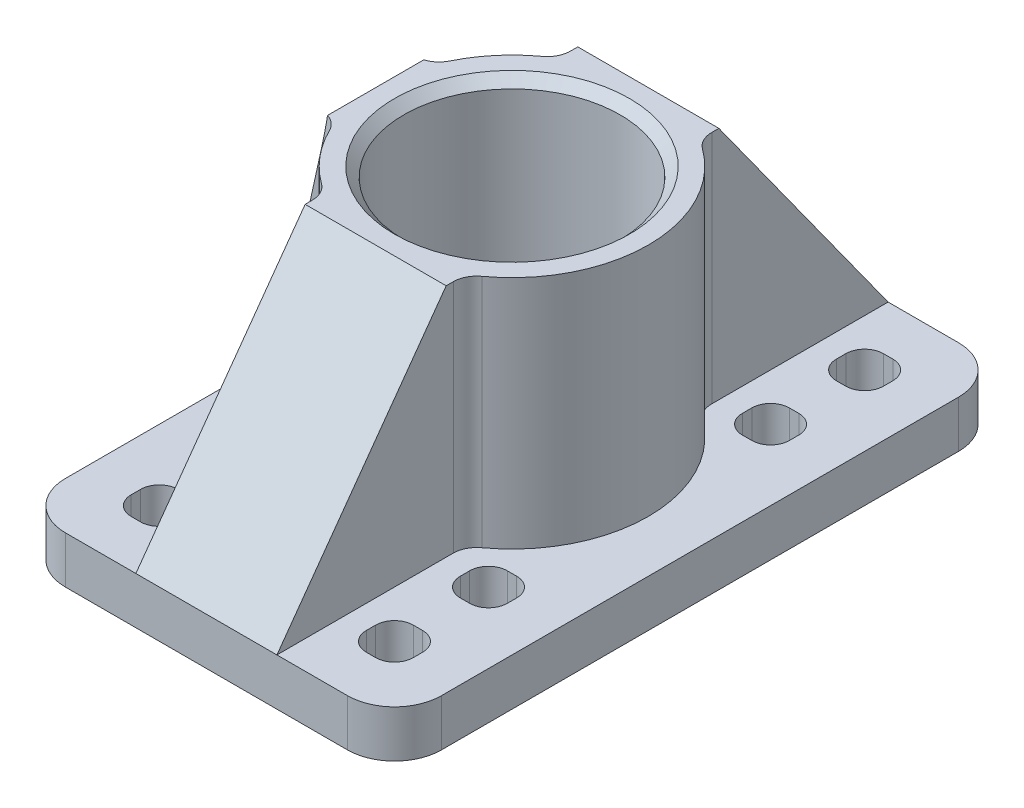
SolidWorks part; units mm, degrees
ref_plane "Front Plane" through (0, 0, 0) normal (0, 0, 1) x (1, 0, 0)
ref_plane "Top Plane" through (0, 0, 0) normal (0, 1, 0) x (1, 0, 0)
ref_plane "Right Plane" through (0, 0, 0) normal (1, 0, 0) x (0, 0, -1)
sketch "Sketch1" plane through (0, 0, 0) normal (0, 1, 0) x (1, 0, 0)
  line L0 (0, 0) -> (9794.4102, 0) construction
  line L1 (0, 0) -> (0, -9794.4102) construction
  line L2 (-12.5, 15) -> (12.5, 15) construction
  line L3 (-15, 17.5) -> (-10, 17.5)
  line L4 (-15, 17.5) -> (-15, 12.5)
  line L5 (-15, 12.5) -> (-10, 12.5)
  line L6 (-10, 17.5) -> (-10, 12.5)
  line L7 (-15, 17.5) -> (-10, 12.5) construction
  line L8 (-15, 12.5) -> (-10, 17.5) construction
  line L9 (12.5, -15) -> (12.5, 15) construction
  line L10 (-12.5, -15) -> (-12.5, 15) construction
  line L11 (-12.5, -15) -> (12.5, -15) construction
  line L12 (-12.5, -15) -> (-12.5, -25) construction
  line L13 (-15, -12.5) -> (-10, -12.5)
  line L14 (-15, -12.5) -> (-15, -17.5)
  line L15 (-15, -17.5) -> (-10, -17.5)
  line L16 (-10, -12.5) -> (-10, -17.5)
  line L17 (-15, -12.5) -> (-10, -17.5) construction
  line L18 (-15, -17.5) -> (-10, -12.5) construction
  line L19 (10, 17.5) -> (15, 17.5)
  line L20 (10, 17.5) -> (10, 12.5)
  line L21 (10, 12.5) -> (15, 12.5)
  line L22 (15, 17.5) -> (15, 12.5)
  line L23 (10, 17.5) -> (15, 12.5) construction
  line L24 (10, 12.5) -> (15, 17.5) construction
  line L25 (10, -12.5) -> (15, -12.5)
  line L26 (10, -12.5) -> (10, -17.5)
  line L27 (10, -17.5) -> (15, -17.5)
  line L28 (15, -12.5) -> (15, -17.5)
  line L29 (10, -12.5) -> (15, -17.5) construction
  line L30 (10, -17.5) -> (15, -12.5) construction
  line L31 (-12.5, -25) -> (12.5, -25) construction
  line L32 (12.5, -25) -> (12.5, -15) construction
  line L33 (-15, 22.5) -> (-10, 27.5) construction
  line L34 (-15, -27.5) -> (-10, -27.5)
  line L35 (-15, -27.5) -> (-15, -22.5)
  line L36 (-15, -22.5) -> (-10, -22.5)
  line L37 (-10, -27.5) -> (-10, -22.5)
  line L38 (-15, -27.5) -> (-10, -22.5) construction
  line L39 (-15, -22.5) -> (-10, -27.5) construction
  line L40 (10, -27.5) -> (15, -27.5)
  line L41 (10, -27.5) -> (10, -22.5)
  line L42 (10, -22.5) -> (15, -22.5)
  line L43 (15, -27.5) -> (15, -22.5)
  line L44 (10, -27.5) -> (15, -22.5) construction
  line L45 (10, -22.5) -> (15, -27.5) construction
  line L46 (-15, 27.5) -> (-10, 22.5) construction
  line L47 (-12.5, 15) -> (-12.5, 25) construction
  line L48 (-10, 27.5) -> (-10, 22.5)
  line L49 (-15, 22.5) -> (-10, 22.5)
  line L50 (-15, 27.5) -> (-15, 22.5)
  line L51 (-15, 27.5) -> (-10, 27.5)
  line L52 (10, 22.5) -> (15, 27.5) construction
  line L53 (10, 27.5) -> (15, 22.5) construction
  line L54 (12.5, 25) -> (12.5, 15) construction
  line L55 (-12.5, 25) -> (12.5, 25) construction
  line L56 (15, 27.5) -> (15, 22.5)
  line L57 (10, 22.5) -> (15, 22.5)
  line L58 (10, 27.5) -> (10, 22.5)
  line L59 (10, 27.5) -> (15, 27.5)
  line L61 (-20, 32.5) -> (20, 32.5)
  line L62 (-20, 32.5) -> (-20, -32.5)
  line L63 (-20, -32.5) -> (20, -32.5)
  line L64 (20, 32.5) -> (20, -32.5)
  line L65 (-20, 32.5) -> (20, -32.5) construction
  line L66 (-20, -32.5) -> (20, 32.5) construction
  point P5 (-12.5, 15)
  point P15 (0, 15)
  point P16 (-12.5, 0)
  point P17 (12.5, 0)
  point P50 (0, 0)
  dimension "D1" = 5
  dimension "D2" = 30
  dimension "D3" = 25
  dimension "D4" = 5
  dimension "D5" = 5
  dimension "D6" = 5
extrude "MountBase" add sketch "Sketch1" along normal blind 5
sketch "Sketch4" plane through (0, 5, 0) normal (0, 1, 0) x (1, 0, 0)
  line L0 (0, 0) -> (50000, 0) construction
  line L1 (0, 0) -> (0, -50000) construction
  line L2 (-14.5, 5) -> (-14.5, -5)
  line L3 (-14.5, -5) -> (-13.6107, -5)
  line L5 (-13.6107, 5) -> (-14.5, 5)
  line L6 (14.5, -5) -> (13.6107, -5)
  line L7 (14.5, 5) -> (14.5, -5)
  line L8 (13.6107, 5) -> (14.5, 5)
  line L9 (-7.5, 14.5) -> (7.5, 14.5)
  line L10 (7.5, 14.5) -> (7.5, 12.4097)
  line L12 (-7.5, 12.4097) -> (-7.5, 14.5)
  line L13 (7.5, -14.5) -> (7.5, -12.4097)
  line L14 (-7.5, -12.4097) -> (-7.5, -14.5)
  line L15 (-7.5, -14.5) -> (7.5, -14.5)
  circle A0 centre (0, 0) radius 11.5
  arc A1 (-13.6107, -5) -> (-7.5, -12.4097) centre (0, 0) ccw
  arc A2 (-13.6107, 5) -> (-14.5, 0) centre (0, 0) ccw construction
  circle A3 centre (0, 0) radius 14.5 construction
  arc A4 (-14.5, 0) -> (-13.6107, -5) centre (0, 0) ccw construction
  arc A5 (-7.5, -12.4097) -> (0, -14.5) centre (0, 0) ccw construction
  arc A6 (7.5, -12.4097) -> (13.6107, -5) centre (0, 0) ccw
  arc A7 (0, -14.5) -> (7.5, -12.4097) centre (0, 0) ccw construction
  arc A8 (13.6107, -5) -> (14.5, 0) centre (0, 0) ccw construction
  arc A9 (13.6107, 5) -> (7.5, 12.4097) centre (0, 0) ccw
  arc A10 (14.5, 0) -> (13.6107, 5) centre (0, 0) ccw construction
  arc A11 (7.5, 12.4097) -> (0, 14.5) centre (0, 0) ccw construction
  arc A12 (-7.5, 12.4097) -> (-13.6107, 5) centre (0, 0) ccw
  arc A13 (0, 14.5) -> (-7.5, 12.4097) centre (0, 0) ccw construction
  point P12 (-14.5, 0)
  point P21 (0, 14.5)
  dimension "D1" = 23
  dimension "D3" = 10
  dimension "D4" = 15
  dimension "D2" = 3
extrude "PipeBase" add sketch "Sketch4" along normal blind 25
sketch "Sketch6" plane through (0, 0, 0) normal (0, 0, 1) x (1, 0, 0)
  line L0 (-14.5, 30) -> (-20, 5)
rib "Rib3" sketch "Sketch6" sketch "Sketch6" thickness 10 extrusion direction parallel to sketch draft on no parameters "D1"=10
mirror "Mirror1" about plane through (0, 0, 0) normal (1, 0, 0) of "Rib3"
sketch "Sketch7" plane through (0, 0, 0) normal (1, 0, 0) x (0, 0, -1)
  line L0 (-14.5, 30) -> (-32.5, 5)
rib "Rib5" sketch "Sketch7" sketch "Sketch7" thickness 15 extrusion direction parallel to sketch draft on no parameters "D1"=15
mirror "Mirror2" about plane through (0, 0, 0) normal (0, 0, 1) of "Rib5"
fillet "BaseFillet" radius 5 4 edges at (20, 2.5, -32.5) (-20, 2.5, -32.5) (-20, 2.5, 32.5) (20, 2.5, 32.5)
fillet "PipeFillet" radius 2.5 8 edges at (-13.6107, 17.5, -5) (-7.5, 17.5, -12.4097) (-13.6107, 17.5, 5) (-7.5, 17.5, 12.4097) (7.5, 17.5, 12.4097) (13.6107, 17.5, 5) (13.6107, 17.5, -5) (7.5, 17.5, -12.4097)
sketch "Sketch8" plane through (0, 5, 0) normal (0, 1, 0) x (1, 0, 0)
  circle A0 centre (0, 0) radius 9
  dimension "D1" = 18
extrude "InnerMaterialRemoval" cut sketch "Sketch8" against normal through all both and the other way through all
chamfer "PipeChamfer" distance 1 angle 45 1 edges at (0, 30, 11.5)
fillet "Fillet5" radius 2 32 edges at (-10, 2.5, -12.5) (-15, 2.5, -12.5) (-15, 2.5, -17.5) (-10, 2.5, -17.5) (-15, 2.5, -27.5) (-10, 2.5, -27.5) (-10, 2.5, -22.5) (-15, 2.5, -22.5) (-10, 2.5, 17.5) (-15, 2.5, 17.5) (-15, 2.5, 12.5) (-10, 2.5, 12.5) (-10, 2.5, 27.5) (-15, 2.5, 27.5) (-15, 2.5, 22.5) (-10, 2.5, 22.5) (10, 2.5, -27.5) (15, 2.5, -27.5) (15, 2.5, -22.5) (10, 2.5, -22.5) (15, 2.5, -12.5) (10, 2.5, -12.5) (15, 2.5, -17.5) (10, 2.5, -17.5) (10, 2.5, 22.5) (10, 2.5, 27.5) (15, 2.5, 27.5) (15, 2.5, 22.5) (10, 2.5, 17.5) (15, 2.5, 17.5) (15, 2.5, 12.5) (10, 2.5, 12.5)
sketch "Sketch9" plane through (0, 30, 0) normal (0, 1, 0) x (1, 0, 0)
  line L0 (7.5, 13.7477) -> (8.2777, 13.7477)
  line L1 (8.2777, 13.7477) -> (20, 7.665)
  line L2 (20, 5) -> (20, 27.5) construction
  line L3 (20, 7.665) -> (20, -7.665)
  line L4 (20, -5) -> (20, 5) construction
  line L5 (-16.5, 0) -> (16.5, 0) construction
  line L6 (8.2777, -13.7477) -> (20, -7.665)
  line L7 (7.5, -13.7477) -> (8.2777, -13.7477)
  circle A0 centre (0, 0) radius 14.5
  arc A1 (13.0126, 6.3971) -> (8.5294, 11.726) centre (0, 0) ccw construction
  arc A2 (8.5294, -11.726) -> (7.5, -13.7477) centre (10, -13.7477) ccw construction
  arc A3 (14.5, -5.1171) -> (13.0126, -6.3971) centre (15.2561, -7.5) ccw construction
  arc A4 (13.0126, 6.3971) -> (15.2561, 5) centre (15.2561, 7.5) ccw construction
  arc A5 (7.5, 13.7477) -> (8.5294, 11.726) centre (10, 13.7477) ccw construction
  arc A6 (8.5294, -11.726) -> (7.5, -13.7477) centre (10, -13.7477) ccw
  arc A7 (14.5, -5.1171) -> (13.0126, -6.3971) centre (15.2561, -7.5) ccw construction
  arc A8 (13.0126, 6.3971) -> (15.2561, 5) centre (15.2561, 7.5) ccw construction
  arc A9 (7.5, 13.7477) -> (8.5294, 11.726) centre (10, 13.7477) ccw
  point P28 (20, 0)
  arc M6 (7.5, -13.7477) -> (8.5294, -11.726) centre (10, -13.7477) cw
  arc M7 (8.5294, -11.726) -> (13.0126, -6.3971) centre (0, 0) ccw
  arc M8 (13.0126, -6.3971) -> (14.5, -5.1171) centre (15.2561, -7.5) cw
  line M9 (14.5, -5.1171) -> (14.5, 5.1171)
  arc M10 (14.5, 5.1171) -> (13.0126, 6.3971) centre (15.2561, 7.5) cw
  arc M11 (13.0126, 6.3971) -> (8.5294, 11.726) centre (0, 0) ccw
  arc M12 (8.5294, 11.726) -> (7.5, 13.7477) centre (10, 13.7477) cw
  dimension "D1" = 15.3301
  dimension "D2" = 0.7777
extrude "Cut-Extrude2" cut sketch "Sketch9" against normal up to surface (25 mm away) from surface contours L7 L6 L3 L1 L0 M6 M12 M11 M10 M9 M8 M7 | A0 M9 M10 | A0 M8 M9 region at (15.4742, 30, 0) region at (14.1348, 30, -4.1081) region at (14.1348, 30, 4.1081) up to face at (13.4645, 5, -16.9044) starting at face at (0, 30, 12.5)
sketch "Sketch10" plane through (0, 0, 0) normal (0, -1, 0) x (1, 0, 0)
  line L0 (0, 0) -> (50000, 0) construction
  line L2 (11, 10) -> (18, 10)
  line L3 (11, 10) -> (11, -10)
  line L4 (11, -10) -> (18, -10)
  line L5 (18, 10) -> (18, -10)
  line L6 (11, 10) -> (18, -10) construction
  line L7 (11, -10) -> (18, 10) construction
  point P3 (14.5, 0)
  dimension "D1" = 7
  dimension "D2" = 20
  dimension "D3" = 14.5
extrude "Cut-Extrude3" cut sketch "Sketch10" against normal blind 3
fillet "Fillet6" radius 2 4 edges at (11, 1.5, -10) (18, 1.5, -10) (18, 1.5, 10) (11, 1.5, 10)
